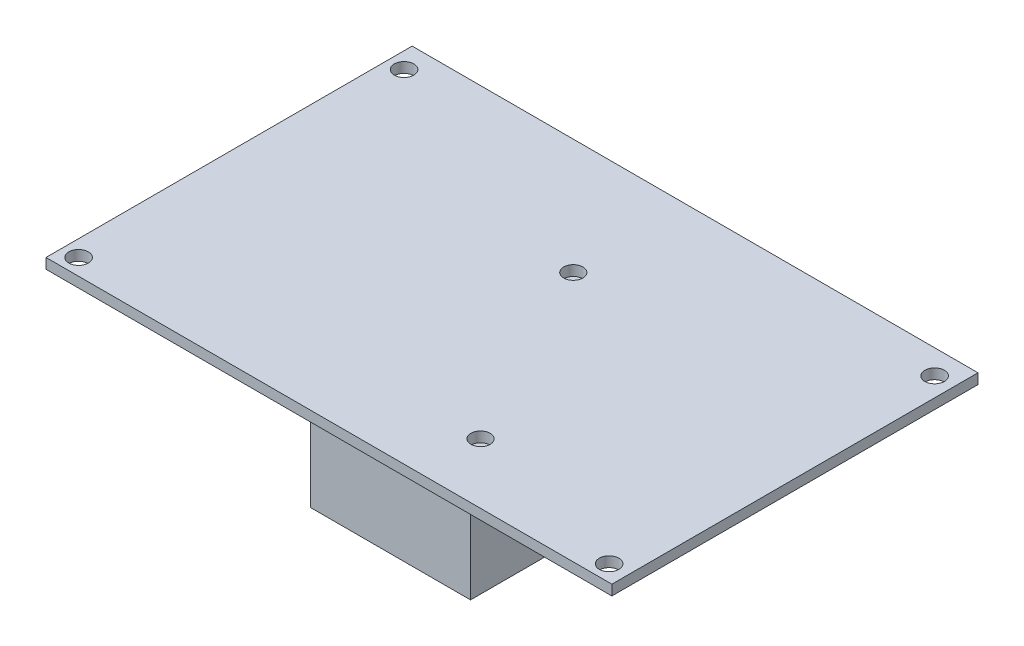
SolidWorks part; units mm, degrees
ref_plane "Přední" through (0, 0, 0) normal (0, 0, 1) x (1, 0, 0)
ref_plane "Horní" through (0, 0, 0) normal (0, 1, 0) x (1, 0, 0)
ref_plane "Pravá" through (0, 0, 0) normal (1, 0, 0) x (0, 0, -1)
sketch "Skica2" plane through (0, 0, 0) normal (0, 1, 0) x (1, 0, 0)
  line L0 (1.524, 8.636) -> (89.84, 8.636)
  line L1 (89.84, 8.636) -> (89.84, 65.776)
  line L2 (89.84, 65.776) -> (1.524, 65.776)
  line L3 (1.524, 65.776) -> (1.524, 8.636)
  circle A0 centre (4.064, 61.976) radius 1.524
  circle A1 centre (4.064, 11.176) radius 1.524
  circle A2 centre (86.868, 11.176) radius 1.524
  circle A3 centre (86.868, 61.976) radius 1.524
  circle A1829 centre (59.944, 18.034) radius 1.5
  circle A1830 centre (44.704, 47.752) radius 1.5
extrude "Přidat vysunutím1" add sketch "Skica2" along normal blind 1.6
sketch "Skica3" plane through (0, 0, 0) normal (0, -1, 0) x (1, 0, 0)
  line L1 (64.3403, -52.5999) -> (39.4023, -52.5999)
  line L2 (64.3403, -52.5999) -> (64.3403, -12.0757)
  line L3 (64.3403, -12.0757) -> (39.4023, -12.0757)
  line L4 (39.4023, -52.5999) -> (39.4023, -12.0757)
extrude "Přidat vysunutím2" add sketch "Skica3" along normal blind 15
